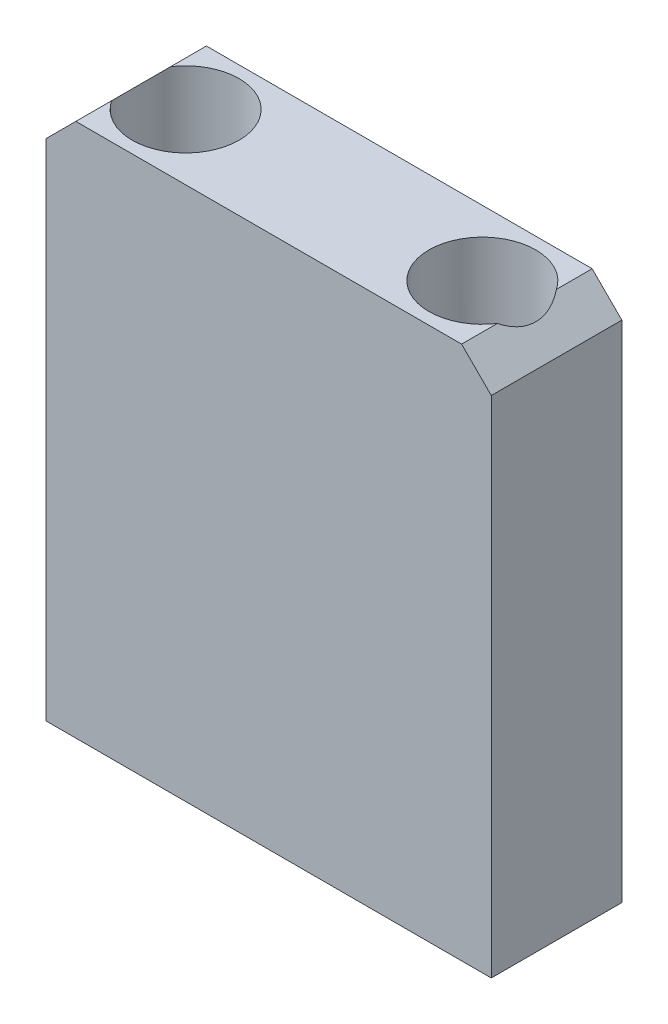
SolidWorks part; units mm, degrees
ref_plane "Front" through (0, 0, 0) normal (0, 0, 1) x (1, 0, 0)
ref_plane "Top" through (0, 0, 0) normal (0, 1, 0) x (1, 0, 0)
ref_plane "Right" through (0, 0, 0) normal (1, 0, 0) x (0, 0, -1)
sketch "Sketch1" plane through (0, 0, 0) normal (0, 0, 1) x (1, 0, 0)
  line L0 (0, -17.291) -> (0, 105.3031) construction
  line L2 (-37.5, 0) -> (37.5, 0)
  line L3 (-37.5, 0) -> (-37.5, 90)
  line L4 (-37.5, 90) -> (37.5, 90)
  line L5 (37.5, 0) -> (37.5, 90)
  dimension "D1" = 75
  dimension "D2" = 90
extrude "Boss-Extrude1" add sketch "Sketch1" along normal blind 22
hole_wizard "CBORE for M10 Socket Head Cap Screw1" positions "Sketch3" profile "Sketch2" counterbore size "M10" standard "JIS" end condition through all
sketch "Sketch3" plane through (0, 90, 0) normal (0, 1, 0) x (-1, 0, 0)
  line L0 (0, -5.9041) -> (0, 28.1906) construction
  line L2 (-37.5, 0) -> (37.5, 0) construction
  point P0 (25, 11)
  point P1 (-25, 11)
  dimension "D1" = 50
  dimension "D2" = 11
sketch "Sketch2" plane through (-25, 90, 11) normal (1, 0, 0) x (0, 0, 1)
  line L0 (0, 0) -> (0, 90)
  line L1 (0, 90) -> (6, 90)
  line L3 (6, 90) -> (6, 31)
  line L4 (6, 31) -> (9, 31)
  line L5 (9, 31) -> (9, 0)
  line L7 (9, 0) -> (0, 0)
  line L11 (0, -6.35) -> (0, 107.95) construction
  dimension "Thru Hole Dia." = 12
  dimension "Thru Hole Depth" = 90
  dimension "C'Bore Dia." = 18
  dimension "C'Bore Depth" = 31
chamfer "Chamfer1" distance 5 angle 45 2 edges at (-37.5, 90, 11) (37.5, 90, 11)
